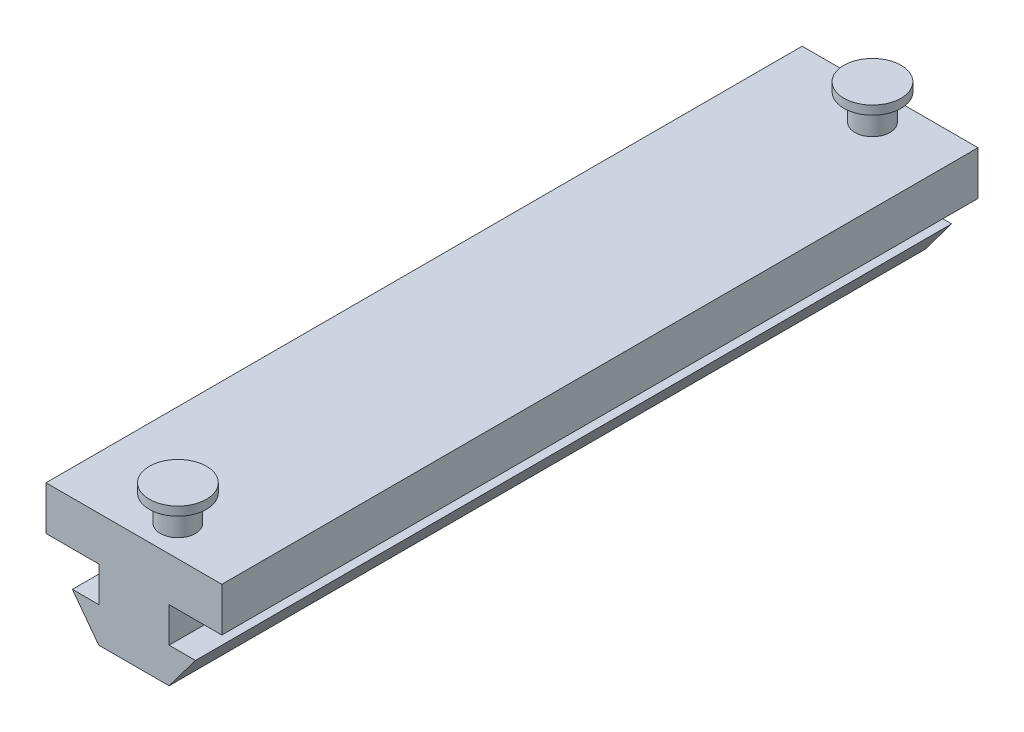
SolidWorks part; units mm, degrees
ref_plane "Front Plane" through (0, 0, 0) normal (0, 0, 1) x (1, 0, 0)
ref_plane "Top Plane" through (0, 0, 0) normal (0, 1, 0) x (1, 0, 0)
ref_plane "Right Plane" through (0, 0, 0) normal (1, 0, 0) x (0, 0, -1)
sketch "Sketch1" plane through (0, 0, 0) normal (0, 1, 0) x (1, 0, 0)
  line L1 (-10, -43) -> (10, -43)
  line L2 (-10, -43) -> (-10, 43)
  line L3 (-10, 43) -> (10, 43)
  line L4 (10, -43) -> (10, 43)
  line L5 (-10, -43) -> (10, 43) construction
  line L6 (-10, 43) -> (10, -43) construction
  point P0 (0, 0)
  dimension "D1" = 20
  dimension "D2" = 86
extrude "Boss-Extrude1" add sketch "Sketch1" along normal blind 5
sketch "Sketch2" plane through (0, 5, 0) normal (0, 1, 0) x (1, 0, 0)
  line L0 (10, 0) -> (-10, 0) construction
  line L1 (10, -43) -> (10, 43) construction
  line L2 (-10, 43) -> (-10, -43) construction
  circle A0 centre (1.5, -39.5) radius 2
  circle A1 centre (1.5, 39.5) radius 2
  point P10 (0, 0)
  dimension "D1" = 4
  dimension "D2" = 11.5
  dimension "D3" = 79
extrude "Boss-Extrude2" add sketch "Sketch2" along normal blind 3
sketch "Sketch3" plane through (0, 8, 0) normal (0, 1, 0) x (1, 0, 0)
  circle A0 centre (1.5, -39.5) radius 3.25
  circle A1 centre (1.5, 39.5) radius 3.25
  dimension "D1" = 6.5
extrude "Boss-Extrude3" add sketch "Sketch3" along normal blind 1
sketch "Sketch4" plane through (0, 0, 43) normal (0, 0, 1) x (1, 0, 0)
  line L0 (0, 0) -> (0, -3) construction
  line L1 (-4, 0) -> (-4, -4)
  line L2 (-10, 0) -> (10, 0) construction
  line L3 (-4, -4) -> (-7, -4)
  line L4 (-7, -4) -> (-4, -8)
  line L5 (-4, -8) -> (4, -8)
  line L6 (4, -8) -> (7, -4)
  line L7 (7, -4) -> (4, -4)
  line L8 (4, -4) -> (4, 0)
  line L9 (-4, 0) -> (4, 0)
  line L10 (0, 5) -> (0, -8) construction
  line L11 (-10, 5) -> (10, 5) construction
  dimension "D1" = 8
  dimension "D2" = 3
  dimension "D3" = 4
  dimension "D4" = 4
extrude "Boss-Extrude4" add sketch "Sketch4" against normal blind 86
